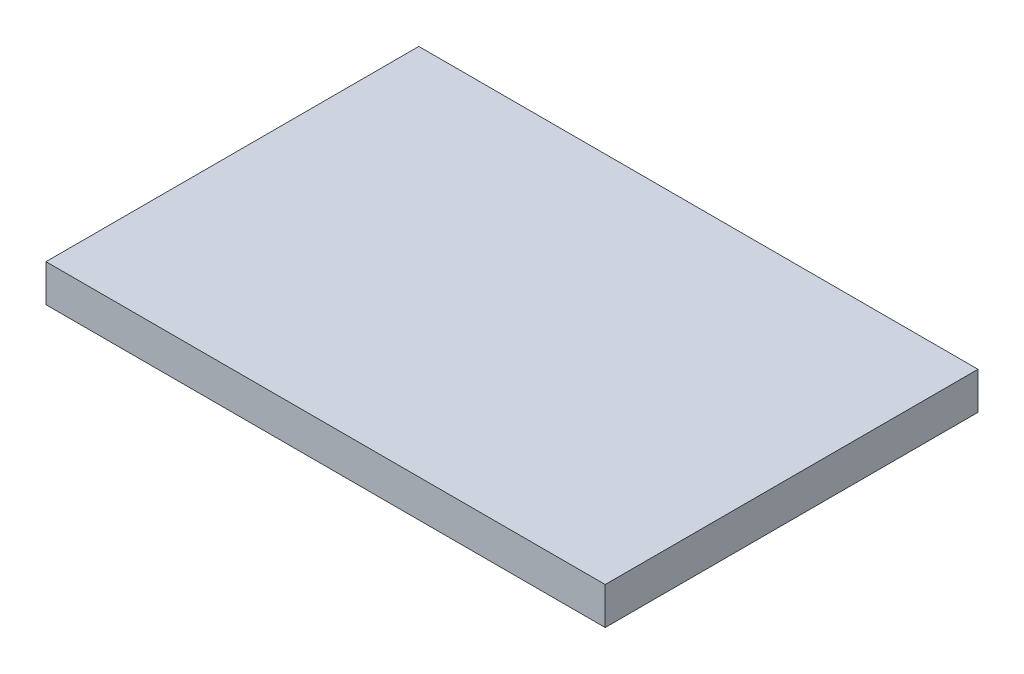
SolidWorks part; units mm, degrees
ref_plane "Front Plane" through (0, 0, 0) normal (0, 0, 1) x (1, 0, 0)
ref_plane "Top Plane" through (0, 0, 0) normal (0, 1, 0) x (1, 0, 0)
ref_plane "Right Plane" through (0, 0, 0) normal (1, 0, 0) x (0, 0, -1)
sketch "Sketch1" plane through (0, 0, 0) normal (0, 1, 0) x (1, 0, 0)
  line L1 (0, -25) -> (75, -25)
  line L2 (0, -25) -> (0, 25)
  line L3 (0, 25) -> (75, 25)
  line L4 (75, -25) -> (75, 25)
  point P5 (0, 0)
  dimension "D1" = 75
  dimension "D2" = 50
extrude "Boss-Extrude1" add sketch "Sketch1" along normal blind 5
